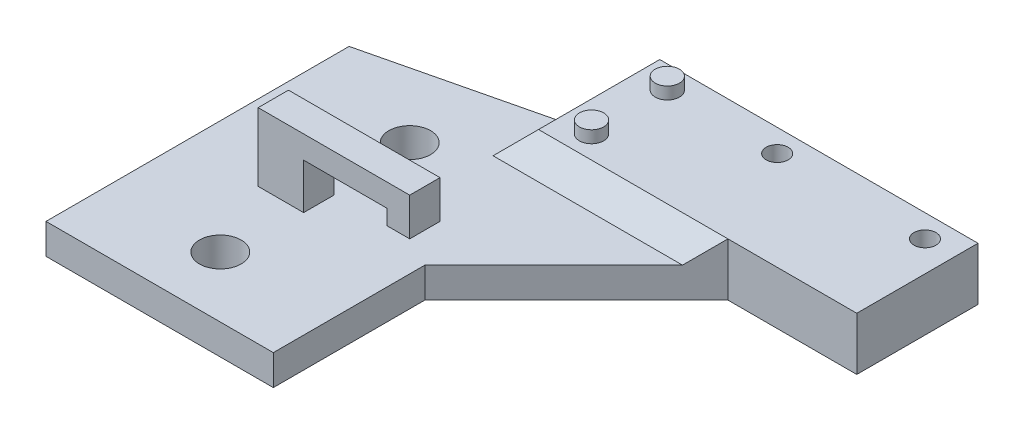
SolidWorks part; units mm, degrees
ref_plane "Front Plane" through (0, 0, 0) normal (0, 0, 1) x (1, 0, 0)
ref_plane "Top Plane" through (0, 0, 0) normal (0, 1, 0) x (1, 0, 0)
ref_plane "Right Plane" through (0, 0, 0) normal (1, 0, 0) x (0, 0, -1)
sketch "Sketch1" plane through (0, 0, 0) normal (0, 1, 0) x (1, 0, 0)
  line L1 (-21, 8) -> (21, 8)
  line L2 (-21, 8) -> (-21, -8)
  line L3 (-21, -8) -> (21, -8)
  line L4 (21, 8) -> (21, -8)
  line L5 (-21, 8) -> (21, -8) construction
  line L6 (-21, -8) -> (21, 8) construction
  point P0 (0, 0)
  dimension "D1" = 42
  dimension "D2" = 16
extrude "Boss-Extrude1" add sketch "Sketch1" along normal blind 7
sketch "Sketch2" plane through (0, 7, 0) normal (0, 1, 0) x (1, 0, 0)
  line L0 (21, 8) -> (-21, 8) construction
  line L1 (-21, -8) -> (21, -8) construction
  line L2 (-21, 8) -> (-21, -8) construction
  circle A0 centre (-17, 5) radius 1.6
  circle A1 centre (-17, -5) radius 1.6
  dimension "D1" = 3.2
  dimension "D2" = 3.2
  dimension "D3" = 3
  dimension "D4" = 3
  dimension "D5" = 4
  dimension "D6" = 4
extrude "Boss-Extrude2" add sketch "Sketch2" along normal blind 1.6
sketch "Sketch3" plane through (0, 0, 0) normal (0, 1, 0) x (1, 0, 0)
  line L0 (21, -8) -> (21, 8) construction
  line L1 (21, 8) -> (-21, 8) construction
  line L2 (-21, 8) -> (-21, -8) construction
  circle A0 centre (-2.5, 5) radius 1.45
  circle A1 centre (17, 5) radius 1.45
  dimension "D5" = 2.9
  dimension "D6" = 2.9
  dimension "D1" = 4
  dimension "D2" = 3
  dimension "D3" = 3
  dimension "D4" = 18.5
extrude "Cut-Extrude1" cut sketch "Sketch3" along normal up to next
sketch "Sketch7" plane through (0, 0, 0) normal (0, 1, 0) x (1, 0, 0)
  line L0 (-21, -2) -> (-46, -8)
  line L1 (-46, -8) -> (-46, -48)
  line L2 (-46, -48) -> (-16, -48)
  line L3 (-16, -48) -> (-16, -28)
  line L4 (-21, -8) -> (21, -8) construction
  line L6 (-21, -8) -> (-21, -2)
  line L7 (-16, -28) -> (4, -8)
  line L8 (4, -8) -> (-21, -8)
  dimension "D1" = 20
  dimension "D2" = 40
  dimension "D3" = 30
  dimension "D4" = 20
  dimension "D5" = 25
  dimension "D6" = 5
  dimension "D7" = 6
extrude "Boss-Extrude6" add sketch "Sketch7" along normal blind 4
sketch "Sketch8" plane through (0, 0, 0) normal (0, 1, 0) x (1, 0, 0)
  line L0 (-46, -48) -> (-16, -48) construction
  line L1 (-46, -8) -> (-46, -48) construction
  circle A0 centre (-31, -40) radius 2.75
  circle A1 centre (-31, -15) radius 2.75
  dimension "D1" = 5.5
  dimension "D2" = 5.5
  dimension "D3" = 8
  dimension "D4" = 25
  dimension "D5" = 15
  dimension "D6" = 15
extrude "Cut-Extrude2" cut sketch "Sketch8" along normal up to next
ref_plane "Plane1" through (0, 0, 28) normal (0, 0, 1) x (1, 0, 0)
sketch "Sketch9" plane through (0, 0, 28) normal (0, 0, 1) x (1, 0, 0)
  line L0 (-36, 4) -> (-36, 13)
  line L1 (-36, 13) -> (-16, 13)
  line L2 (-16, 13) -> (-16, 8)
  line L3 (-16, 8) -> (-19, 8)
  line L4 (-19, 8) -> (-19, 10)
  line L5 (-19, 10) -> (-30, 10)
  line L6 (-30, 10) -> (-30, 4)
  line L7 (-46, 4) -> (-16, 4) construction
  line L8 (-30, 4) -> (-36, 4)
  line L9 (-46, 4) -> (-46, 0) construction
  dimension "D1" = 6
  dimension "D2" = 9
  dimension "D3" = 5
  dimension "D4" = 2
  dimension "D5" = 3
  dimension "D6" = 20
  dimension "D7" = 10
extrude "Boss-Extrude7" add sketch "Sketch9" along normal mid plane 4
chamfer "Chamfer2" distance 3 angle 45 2 edges at (-21, 4, 5) (-8.5, 4, 8)
